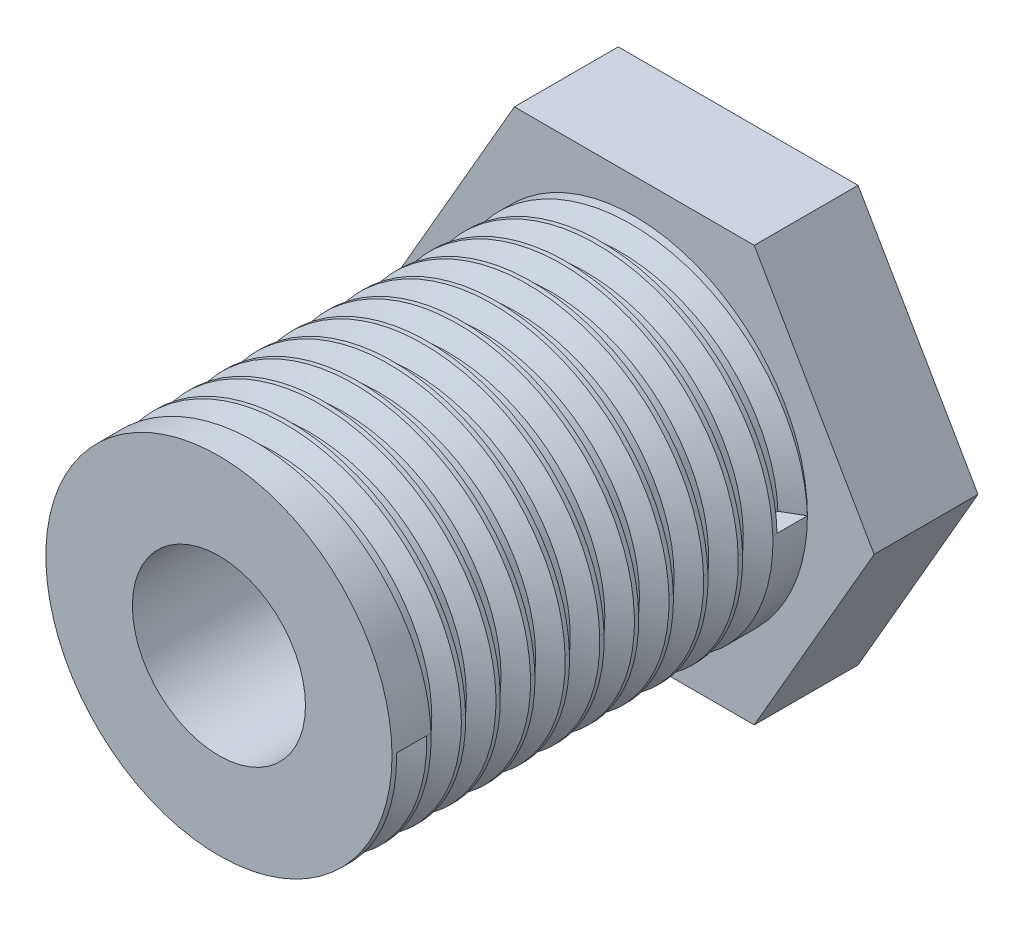
SolidWorks part; units mm, degrees
ref_plane "Front Plane" through (0, 0, 0) normal (0, 0, 1) x (1, 0, 0)
ref_plane "Top Plane" through (0, 0, 0) normal (0, 1, 0) x (1, 0, 0)
ref_plane "Right Plane" through (0, 0, 0) normal (1, 0, 0) x (0, 0, -1)
sketch "Sketch1" plane through (0, 0, 0) normal (0, 0, 1) x (1, 0, 0)
  line L1 (6.9282, 0) -> (3.4641, 6)
  line L2 (3.4641, 6) -> (-3.4641, 6)
  line L3 (-3.4641, 6) -> (-6.9282, 0)
  line L4 (-6.9282, 0) -> (-3.4641, -6)
  line L5 (-3.4641, -6) -> (3.4641, -6)
  line L6 (3.4641, -6) -> (6.9282, 0)
  circle A0 centre (0, 0) radius 6 construction
  dimension "D1" = 12
extrude "Boss-Extrude1" add sketch "Sketch1" along normal blind 3
sketch "Sketch2" plane through (0, 0, 3) normal (0, 0, 1) x (1, 0, 0)
  circle A0 centre (0, 0) radius 5
  dimension "D1" = 10
extrude "Boss-Extrude2" add sketch "Sketch2" along normal blind 12
sketch "Sketch3" plane through (0, 0, 15) normal (0, 0, 1) x (1, 0, 0)
  circle A0 centre (0, 0) radius 2.5
  dimension "D1" = 5
extrude "Cut-Extrude1" cut sketch "Sketch3" against normal through all
thread "Thread1" pitch 1 method cut profile "Thread Profile2" start angle 0, offset 0, length 11, pitch 1, diameter 10
ref_plane "Plane2" through (5, 0, 3) normal (0, -1, 0) x (1, 0, 0)
sketch "Thread Profile2" plane through (5, 0, 3) normal (0, -1, 0) x (1, 0, 0)
  line L0 (0, 0) -> (0, 1) construction
  line L11 (0, 0) -> (0, 0.875)
  line L12 (0, 0.875) -> (-0.5413, 0.5625)
  line L13 (-0.5413, 0.5625) -> (-0.5413, 0.3125)
  line L15 (-0.5413, 0.3125) -> (0, 0)
  line L17 (-0.5413, 0.4375) -> (0, 0.4375) construction
  point P2 (0, 0)
  dimension "Pitch" = 1
  dimension "Profile_Angle" = 60
  dimension "Profile_Land" = 0.25
  dimension "Profile_Height" = 0.5413
